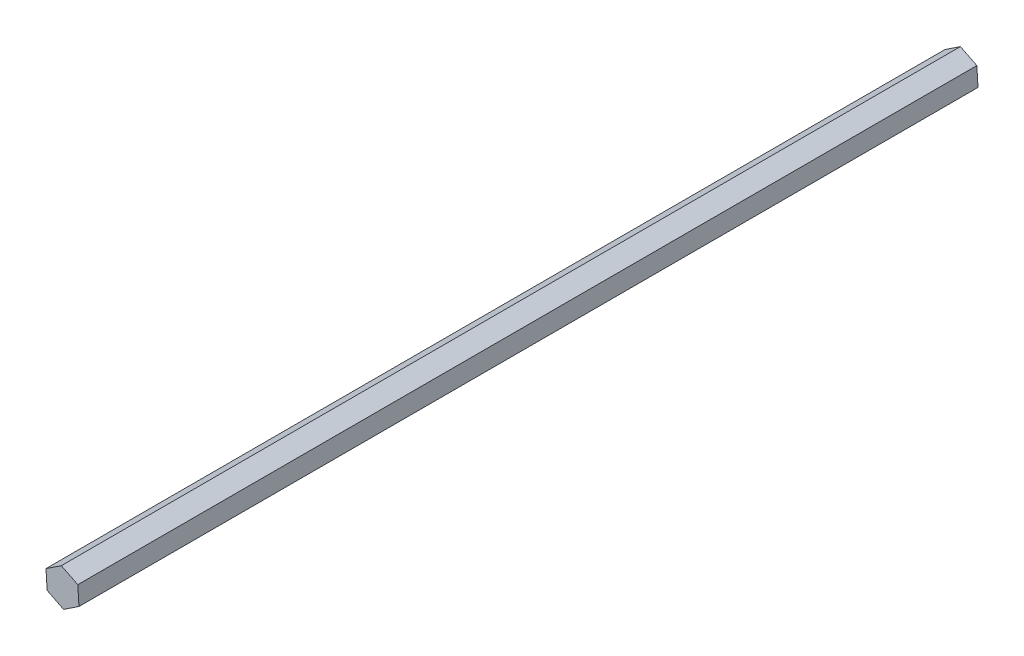
SolidWorks part; units mm, degrees
ref_plane "Front Plane" through (0, 0, 0) normal (0, 0, 1) x (1, 0, 0)
ref_plane "Top Plane" through (0, 0, 0) normal (0, 1, 0) x (1, 0, 0)
ref_plane "Right Plane" through (0, 0, 0) normal (1, 0, 0) x (0, 0, -1)
sketch "Sketch1" plane through (0, 0, 0) normal (0, 0, 1) x (1, 0, 0)
  line L1 (-0.4538, 7.336) -> (-6.58, 3.275)
  line L2 (-6.58, 3.275) -> (-6.1263, -4.061)
  line L3 (-6.1263, -4.061) -> (0.4538, -7.336)
  line L4 (0.4538, -7.336) -> (6.58, -3.275)
  line L5 (6.58, -3.275) -> (6.1263, 4.061)
  line L6 (6.1263, 4.061) -> (-0.4538, 7.336)
  circle A0 centre (0, 0) radius 6.3653 construction
  dimension "D1" = 7.35
extrude "Boss-Extrude1" add sketch "Sketch1" along normal blind 359.1
